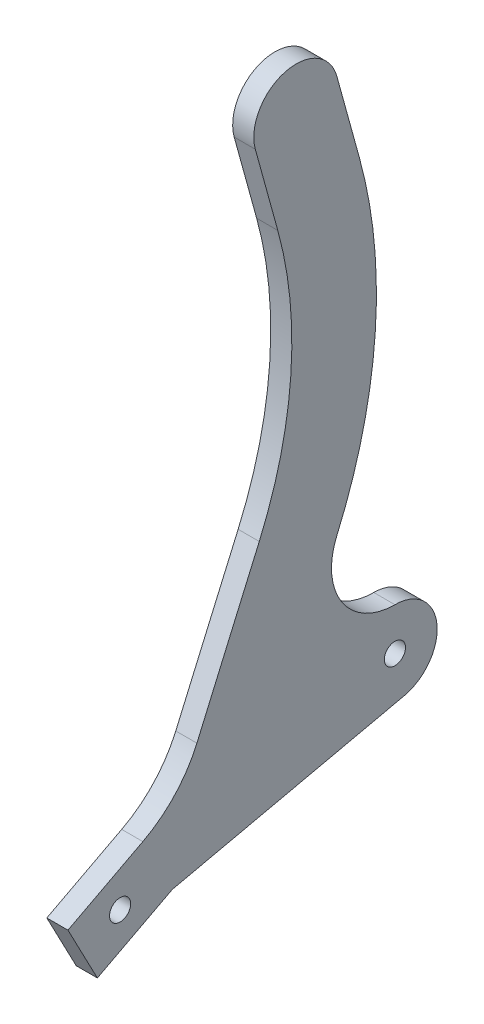
SolidWorks part; units mm, degrees
ref_plane "Front Plane" through (0, 0, 0) normal (0, 0, 1) x (1, 0, 0)
ref_plane "Top Plane" through (0, 0, 0) normal (0, 1, 0) x (1, 0, 0)
ref_plane "Right Plane" through (0, 0, 0) normal (1, 0, 0) x (0, 0, -1)
sketch "Sketch1" plane through (0, 0, 0) normal (1, 0, 0) x (0, 0, -1)
  line L1 (0, 0) -> (-50.8, 0) construction
  line L2 (-50.8, 0) -> (-50.8, 136.525) construction
  line L3 (-75.7219, -11.0685) -> (-98.2201, -22.8578)
  line L4 (-98.2201, -22.8578) -> (-89.3781, -39.7315)
  line L5 (-89.3781, -39.7315) -> (-66.8799, -27.9422)
  line L6 (-93.7991, -31.2947) -> (-82.55, -25.4) construction
  line L8 (0, 0) -> (-38.5565, 139.8993) construction
  line L9 (-38.5565, 139.8993) -> (-41.9308, 152.1429)
  line L10 (-38.5565, 139.8993) -> (-35.1821, 127.6558)
  line L12 (0, 12.7) -> (0, 0) construction
  line L14 (-41.9308, 152.1429) -> (-17.4438, 158.8915) construction
  line L15 (-17.4438, 158.8915) -> (-10.6951, 134.4045)
  line L16 (-35.1821, 127.6558) -> (-10.6951, 134.4045) construction
  line L17 (-66.8799, -27.9422) -> (2.7669, -12.3949)
  line L19 (-17.4628, 39.3627) -> (-40.7465, 49.513) construction
  line L20 (-40.7465, 49.513) -> (-32.7787, 67.7904) construction
  circle A0 centre (0, 0) radius 3.175
  arc A1 (2.7669, -12.3949) -> (0, 12.7) centre (0, 0) ccw
  circle A2 centre (-50.8, 136.525) radius 4.7625 construction
  circle A3 centre (-50.8, 136.525) radius 12.7 construction
  circle A4 centre (-82.55, -25.4) radius 3.175
  arc A11 (-41.9308, 152.1429) -> (-17.4438, 158.8915) centre (-29.6873, 155.5172) cw
  arc A12 (0, 12.7) -> (-17.4628, 39.3627) centre (0, 31.75) cw
  arc A15 (-35.1821, 127.6558) -> (-40.7465, 49.513) centre (-148.413, 96.4492) cw
  arc A16 (-10.6951, 134.4045) -> (-17.4628, 39.3627) centre (-148.413, 96.4492) cw
  arc A17 (-40.7465, 49.513) -> (-59.4812, 6.4149) centre (20579.8884, -8939.8513) ccw
  arc A19 (-59.4812, 6.4149) -> (-75.7219, -11.0685) centre (-92.3488, 20.6616) cw
  dimension "D1" = 6.35
  dimension "D2" = 25.4
  dimension "D3" = 50.8
  dimension "D5" = 9.525
  dimension "D6" = 25.4
  dimension "D8" = 6.35
  dimension "D10" = 25.4
  dimension "D11" = 25.4
  dimension "D13" = 12.7
  dimension "D14" = 82.55
  dimension "D15" = 25.4
  dimension "D16" = 19.05
  dimension "D12" = 12.7
  dimension "D18" = 25.4
  dimension "D4" = 136.525
  dimension "D7" = 19.05
  dimension "D9" = 12.7
extrude "Boss-Extrude1" add sketch "Sketch1" along normal blind 6.35
